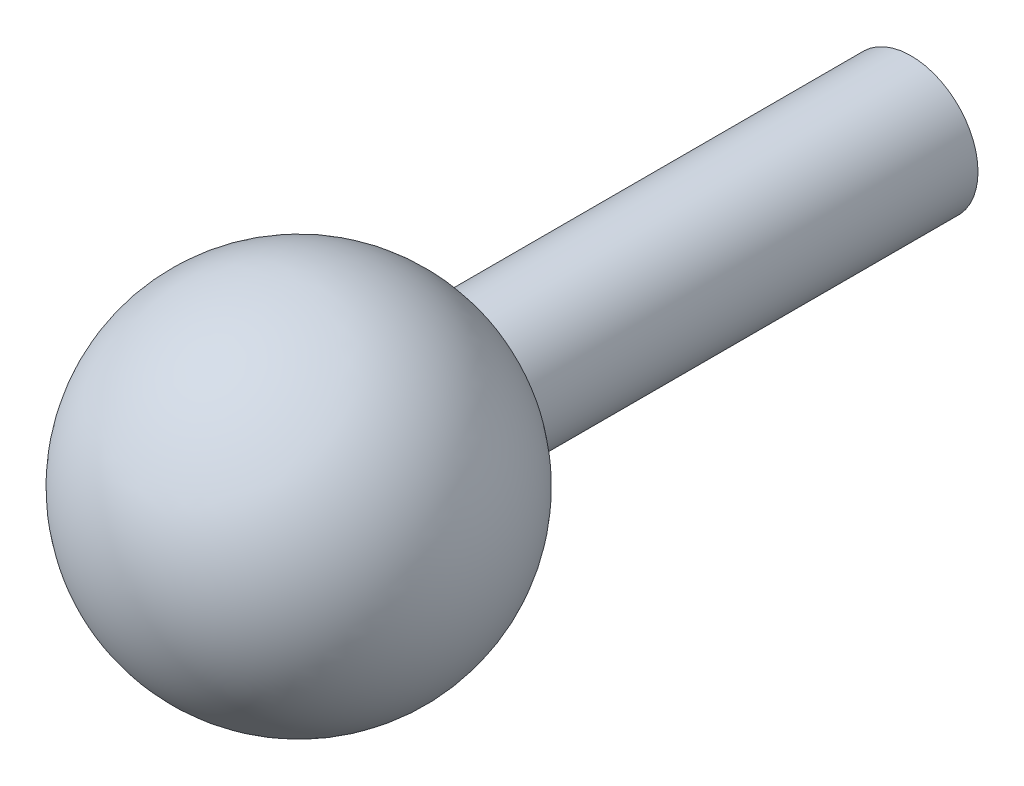
SolidWorks part; units mm, degrees
ref_plane "Front Plane" through (0, 0, 0) normal (0, 0, 1) x (1, 0, 0)
ref_plane "Top Plane" through (0, 0, 0) normal (0, 1, 0) x (1, 0, 0)
ref_plane "Right Plane" through (0, 0, 0) normal (1, 0, 0) x (0, 0, -1)
sketch "Sketch1" plane through (0, 0, 0) normal (0, 0, 1) x (1, 0, 0)
  circle A0 centre (0, 0) radius 9.525
  dimension "D1" = 19.05
extrude "Boss-Extrude1" add sketch "Sketch1" along normal blind 63.5
sketch "Sketch2" plane through (0, 0, 0) normal (1, 0, 0) x (0, 0, -1)
  line L0 (-63.5, 0) -> (-112.4464, 0)
  line L1 (-63.5, 9.525) -> (-63.5, -9.525) construction
  line L2 (-63.5, 9.525) -> (-63.5, 0)
  arc A1 (-112.4464, 0) -> (-63.5, 9.525) centre (-87.0464, 0) cw
  dimension "D1" = 25.4
revolve "Revolve1" add sketch "Sketch2" angle 360 about L0
sketch "Sketch3" plane through (0, 0, 0) normal (0, 0, -1) x (-1, 0, 0)
  line L1 (-0.55, 1.25) -> (0.55, 1.25)
  line L2 (-0.55, 1.25) -> (-0.55, -1.25)
  line L3 (-0.55, -1.25) -> (0.55, -1.25)
  line L4 (0.55, 1.25) -> (0.55, -1.25)
  point P2 (0.55, 0)
  point P5 (0, 1.25)
  dimension "D1" = 1.1
  dimension "D2" = 2.5
extrude "Cut-Extrude1" cut sketch "Sketch3" against normal blind 5
